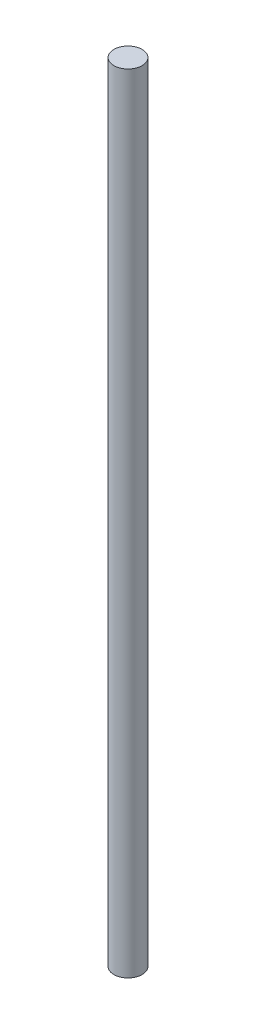
SolidWorks part; units mm, degrees
material "1060 Alloy"
ref_plane "Front Plane" through (0, 0, 0) normal (0, 0, 1) x (1, 0, 0)
ref_plane "Top Plane" through (0, 0, 0) normal (0, 1, 0) x (1, 0, 0)
ref_plane "Right Plane" through (0, 0, 0) normal (1, 0, 0) x (0, 0, -1)
sketch "Sketch1" plane through (0, 0, 0) normal (0, 1, 0) x (1, 0, 0)
  circle A0 centre (0, 0) radius 5
  dimension "D1" = 10
extrude "Boss-Extrude1" add sketch "Sketch1" along normal blind 279.4
